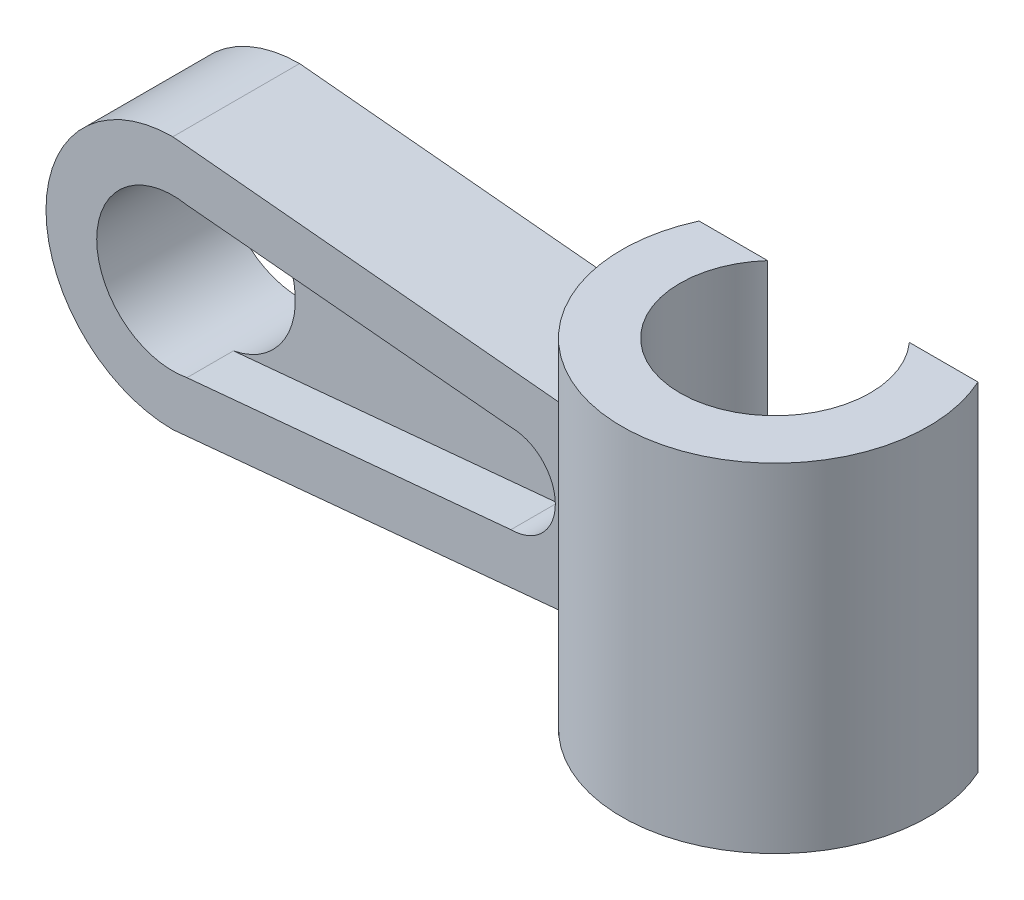
SolidWorks part; units mm, degrees
ref_plane "Plan de face" through (0, 0, 0) normal (0, 0, 1) x (1, 0, 0)
ref_plane "Plan de dessus" through (0, 0, 0) normal (0, 1, 0) x (1, 0, 0)
ref_plane "Plan de droite" through (0, 0, 0) normal (1, 0, 0) x (0, 0, -1)
sketch "Esquisse1" plane through (0, 0, 0) normal (0, 0, 1) x (1, 0, 0)
  line L0 (0, 6) -> (21, 4)
  line L1 (21, 4) -> (21, -4)
  line L2 (21, -4) -> (0, -6)
  line L3 (0, 0) -> (21, 0) construction
  circle A0 centre (0, 0) radius 6 construction
  circle A1 centre (21, 0) radius 4 construction
  arc A2 (0, -6) -> (0, 6) centre (0, 0) cw
  point P10 (0, -6)
  point P11 (0, -6)
  point P12 (0, -6)
  dimension "D1" = 12
  dimension "D3" = 8
  dimension "D2" = 21
extrude "Boss.-Extru.1" add sketch "Esquisse1" along normal blind 6
sketch "Esquisse2" plane through (0, 0, 0) normal (0, 0, -1) x (-1, 0, 0)
  circle A0 centre (0, 0) radius 3.6
  dimension "D1" = 7.2
extrude "Enlèv. mat.-Extru.1" cut sketch "Esquisse2" against normal up to next
sketch "Esquisse3" plane through (0, 0, 6) normal (0, 0, 1) x (1, 0, 0)
  line L0 (0, 0) -> (16, 0) construction
  line L1 (0, 3.6) -> (16, 2.1)
  line L2 (0, -3.6) -> (16, -2.1)
  circle A0 centre (16, 0) radius 2.1 construction
  circle A1 centre (0, 0) radius 3.6 construction
  arc A2 (0, -3.6) -> (0, 3.6) centre (0, 0) cw
  arc A3 (16, -2.1) -> (16, 2.1) centre (16, 0) ccw
  dimension "D1" = 4.2
  dimension "D3" = 7.2
  dimension "D2" = 16
extrude "Enlèv. mat.-Extru.2" cut sketch "Esquisse3" against normal blind 2.2
sketch "Esquisse4" plane through (0, 0, 0) normal (0, 1, 0) x (1, 0, 0)
  line L0 (21, 0) -> (0, 0) construction
  line L1 (18.25, 0) -> (21, 0)
  line L2 (18.25, 0) -> (18.25, -6)
  line L3 (18.25, -6) -> (21, -6)
  line L4 (21, 0) -> (21, -6)
  line L5 (18.25, 0) -> (21, -6) construction
  line L6 (18.25, -6) -> (21, 0) construction
  line L7 (21, -6) -> (21, 0) construction
  point P4 (19.625, -3)
  dimension "D1" = 2.75
extrude "Boss.-Extru.2" [suppressed] add sketch "Esquisse4" along normal blind 22.2 and the other way blind 5
sketch "Esquisse5" [suppressed] plane through (0, 22.2, 0) normal (0, 1, 0) x (1, 0, 0)
  line L0 (21, -6) -> (21, 0)
  arc A0 (21, -6) -> (21, 0) centre (24, -3) cw
  dimension "D1" = 4.2426
extrude "Enlèv. mat.-Extru.3" [suppressed] cut sketch "Esquisse5" against normal up to next
fillet "Congé1" [suppressed] radius 3
fillet "Congé2" [suppressed] radius 3
ref_plane "Plan1" through (0, 0, 3) normal (0, 0, 1) x (1, 0, 0)
sketch "Esquisse6" plane through (0, 0, 3) normal (0, 0, 1) x (1, 0, 0)
  line L0 (21, -4) -> (21, 4) construction
  line L1 (18.25, 9) -> (21, 9)
  line L2 (18.25, 9) -> (18.25, -7)
  line L3 (18.25, -7) -> (21, -7)
  line L4 (21, 9) -> (21, -7)
  line L5 (18.25, 9) -> (21, -7) construction
  line L6 (18.25, -7) -> (21, 9) construction
  line L7 (25.5, 9) -> (25.5, -7) construction
  point P4 (19.625, 1)
  dimension "D1" = 2.75
  dimension "D2" = 3
  dimension "D3" = 5
  dimension "D4" = 4.5
revolve "Révolution1" add sketch "Esquisse6" angle 360 about L7 reverse direction yes
sketch "Esquisse7" plane through (0, 0, 0) normal (0, 0, -1) x (-1, 0, 0)
  line L1 (-15.6103, -17.1672) -> (-45.1653, -17.1672)
  line L2 (-15.6103, -17.1672) -> (-15.6103, 19.4792)
  line L3 (-15.6103, 19.4792) -> (-45.1653, 19.4792)
  line L4 (-45.1653, -17.1672) -> (-45.1653, 19.4792)
  line L5 (-15.6103, -17.1672) -> (-45.1653, 19.4792) construction
  line L6 (-15.6103, 19.4792) -> (-45.1653, -17.1672) construction
  point P4 (-30.3878, 1.156)
extrude "Enlèv. mat.-Extru.4" cut sketch "Esquisse7" along normal up to next
